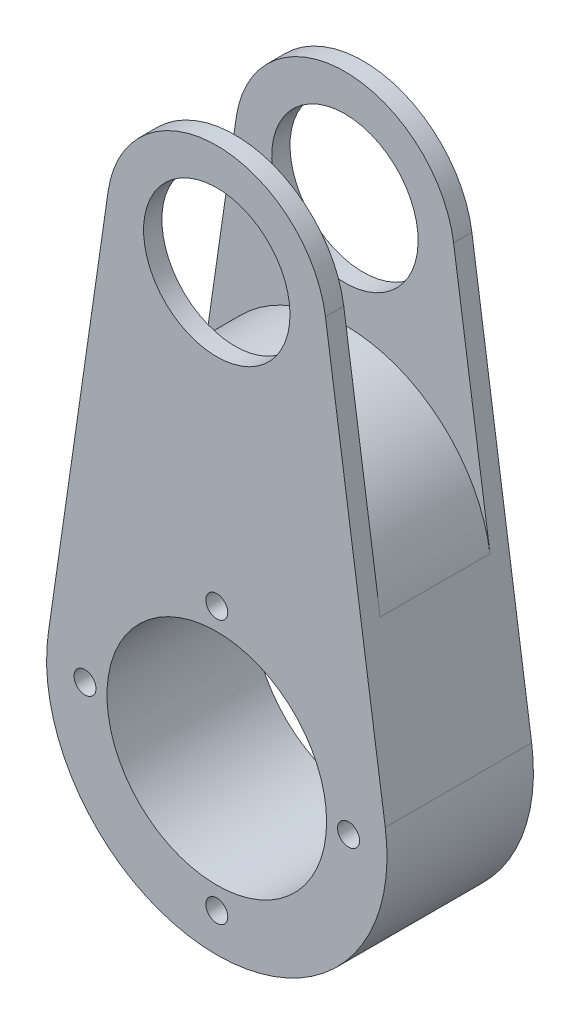
SolidWorks part; units mm, degrees
ref_plane "Alzado" through (0, 0, 0) normal (0, 0, 1) x (1, 0, 0)
ref_plane "Planta" through (0, 0, 0) normal (0, 1, 0) x (1, 0, 0)
ref_plane "Vista lateral" through (0, 0, 0) normal (1, 0, 0) x (0, 0, -1)
sketch "Croquis1" plane through (0, 0, 0) normal (0, 0, 1) x (1, 0, 0)
  line L0 (0, -17.338) -> (0, 18.662) construction
  line L1 (18, 0.662) -> (-18, 0.662) construction
  line L2 (0, 0.662) -> (0, 58.162) construction
  line L3 (-23.0094, 3.9979) -> (-14.8448, 60.3142)
  line L5 (23.0094, 3.9979) -> (14.8448, 60.3142)
  circle A0 centre (0, 0.662) radius 15
  circle A2 centre (0, 18.662) radius 1.5
  circle A3 centre (18, 0.662) radius 1.5
  circle A4 centre (0, -17.338) radius 1.5
  circle A5 centre (-18, 0.662) radius 1.5
  arc A6 (14.8448, 60.3142) -> (-14.8448, 60.3142) centre (0, 58.162) ccw
  arc A7 (-23.0094, 3.9979) -> (23.0094, 3.9979) centre (0, 0.662) ccw
  circle A8 centre (0, 58.162) radius 10
  point P7 (0, 0.662)
  point P11 (0, 0.662)
  dimension "D1" = 46.5
  dimension "D2" = 30
  dimension "D4" = 3
  dimension "D6" = 30
  dimension "D7" = 20
  dimension "D3" = 18
  dimension "D5" = 57.5
extrude "Saliente-Extruir1" add sketch "Croquis1" along normal mid plane 20
sketch "Croquis3" plane through (0, 0, 0) normal (1, 0, 0) x (0, 0, -1)
  line L0 (0, 73.162) -> (7.5, 73.162)
  line L1 (10, 73.162) -> (-10, 73.162) construction
  line L2 (7.5, 73.162) -> (7.5, 43.162)
  line L3 (7.5, 43.162) -> (-7.5, 43.162)
  line L4 (-7.5, 43.162) -> (-7.5, 73.162)
  line L5 (-7.5, 73.162) -> (0, 73.162)
  dimension "D1" = 15
  dimension "D2" = 30
extrude "Cortar-Extruir2" cut sketch "Croquis3" against normal through all both and the other way through all
fillet "Redondeo3" radius 20 2 edges at (17.3315, 43.162, 0) (-17.3315, 43.162, 0)
